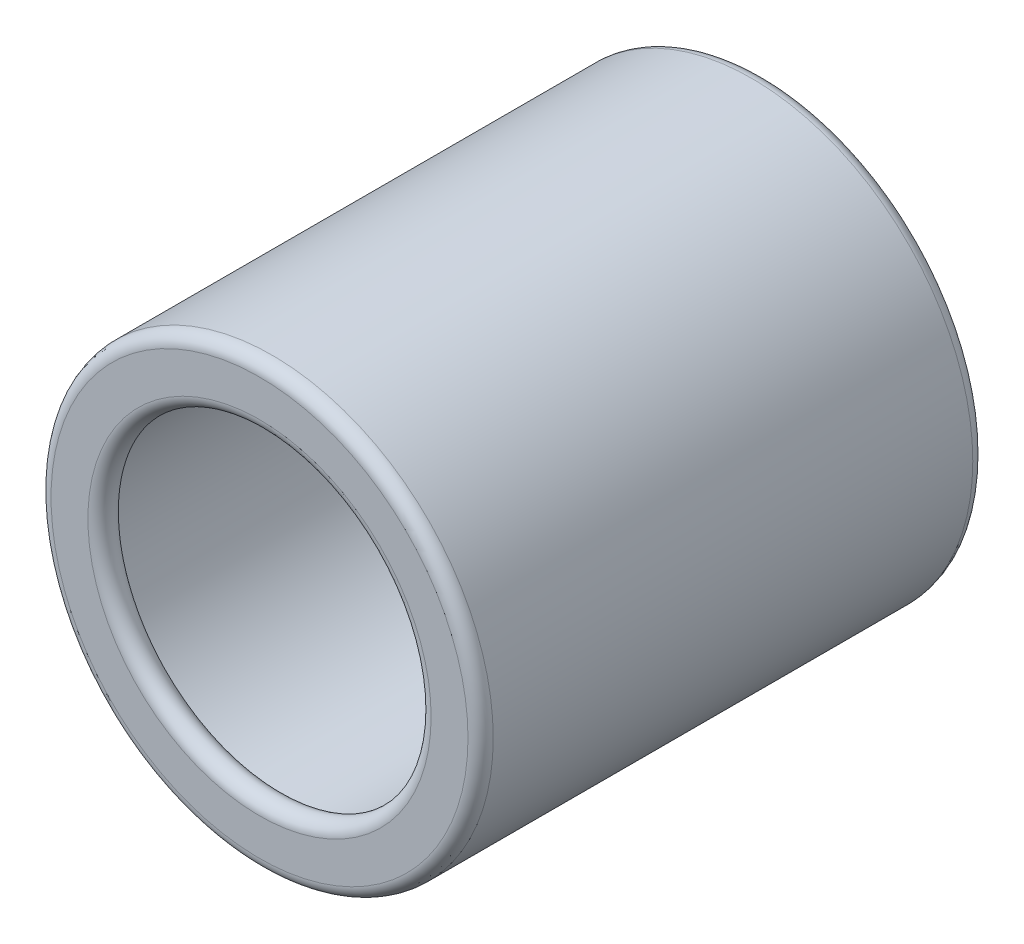
SolidWorks part; units mm, degrees
material "ABS"
ref_plane "Front Plane" through (0, 0, 0) normal (0, 0, 1) x (1, 0, 0)
ref_plane "Top Plane" through (0, 0, 0) normal (0, 1, 0) x (1, 0, 0)
ref_plane "Right Plane" through (0, 0, 0) normal (1, 0, 0) x (0, 0, -1)
sketch "Sketch1" plane through (0, 0, 0) normal (0, 0, 1) x (1, 0, 0)
  circle A0 centre (0, 0) radius 13.9065
  circle A1 centre (0, 0) radius 10
  dimension "D1" = 27.813
  dimension "D2" = 20
extrude "Boss-Extrude1" add sketch "Sketch1" along normal blind 31.75
fillet "Fillet1" radius 0.7937 4 edges at (10, 0, 0) (13.9065, 0, 0) (13.9065, 0, 31.75) (10, 0, 31.75)
other "Move Face3" flip direction yes face at (10, 0, 30.9563) offset 0.635 parameters "D1"=0.635
equation "\"D1@Sketch1\"=1.125in-0.015*2"
